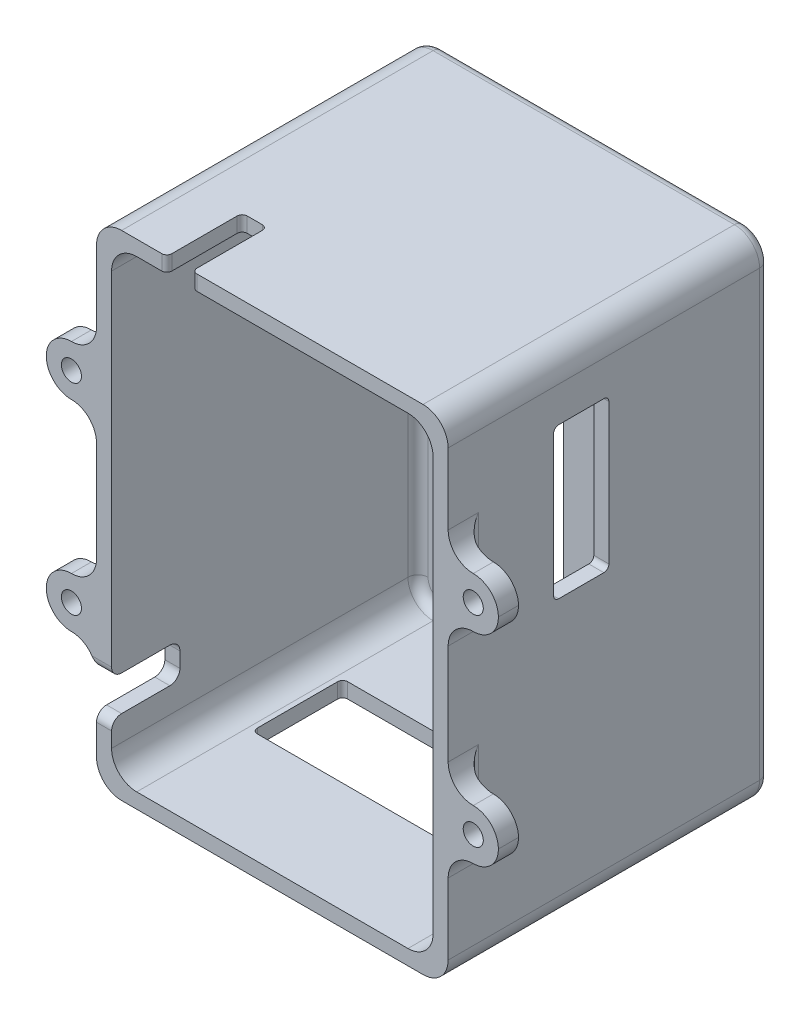
SolidWorks part; units mm, degrees
ref_plane "Front Plane" through (0, 0, 0) normal (0, 0, 1) x (1, 0, 0)
ref_plane "Top Plane" through (0, 0, 0) normal (0, 1, 0) x (1, 0, 0)
ref_plane "Right Plane" through (0, 0, 0) normal (1, 0, 0) x (0, 0, -1)
sketch "Sketch1" plane through (0, 0, 0) normal (0, 0, 1) x (1, 0, 0)
  line L1 (32, -46.1468) -> (-32, -46.1468)
  line L2 (32, -46.1468) -> (32, 46.1468)
  line L3 (32, 46.1468) -> (-32, 46.1468)
  line L4 (-32, -46.1468) -> (-32, 46.1468)
  line L5 (32, -46.1468) -> (-32, 46.1468) construction
  line L6 (32, 46.1468) -> (-32, -46.1468) construction
  line L12 (-19, -38.1468) -> (-29, -38.1468)
  line L13 (-19, -38.1468) -> (-19, 38.1468)
  line L14 (-19, 38.1468) -> (-29, 38.1468)
  line L15 (-29, -38.1468) -> (-29, 38.1468)
  line L16 (-19, -38.1468) -> (-29, 38.1468) construction
  line L17 (-19, 38.1468) -> (-29, -38.1468) construction
  line L69 (-3, -38.1468) -> (-3, 38.1468)
  line L70 (-3, -38.1468) -> (-13, -38.1468)
  line L71 (-13, -38.1468) -> (-13, 38.1468)
  line L72 (-3, 38.1468) -> (-13, 38.1468)
  line L73 (13, -38.1468) -> (13, 38.1468)
  line L74 (13, -38.1468) -> (3, -38.1468)
  line L75 (3, -38.1468) -> (3, 38.1468)
  line L76 (13, 38.1468) -> (3, 38.1468)
  line L100 (29, -38.1468) -> (29, 38.1468)
  line L101 (35, -49.1468) -> (-35, -49.1468)
  line L102 (35, -49.1468) -> (35, 49.1468)
  line L103 (35, 49.1468) -> (-35, 49.1468)
  line L104 (-35, -49.1468) -> (-35, 49.1468)
  line L105 (35, -49.1468) -> (-35, 49.1468) construction
  line L106 (35, 49.1468) -> (-35, -49.1468) construction
  line L107 (29, -38.1468) -> (19, -38.1468)
  line L108 (19, -38.1468) -> (19, 38.1468)
  line L109 (29, 38.1468) -> (19, 38.1468)
  point P0 (0, 0)
  point P7 (0, 0)
  point P8 (-24, 0)
  dimension "D1" = 64
  dimension "D2" = 8
  dimension "D3" = 8
  dimension "D4" = 3
  dimension "D5" = 10
  dimension "D6" = 3
  dimension "D8" = 3
  dimension "D9" = 3
  dimension "D10" = 92.2936
  dimension "D7" = 4
extrude "Boss-Extrude1" add sketch "Sketch1" along normal blind 3 contours L4 L1 L2 L3 L107 L12 L15 L14 L13 L74 region at (0, 0, 0)
extrude "Boss-Extrude2" add sketch "Sketch1<3>" along normal blind 64 contours L104 L101 L102 L103 L1 L4 L3 L2 region at (0, -47.9401, 0)
sketch "Sketch1<3>" plane through (0, 0, 0) normal (0, 0, 1) x (1, 0, 0) same geometry as "Sketch1"
fillet "Fillet1" radius 2 16 edges at (-29, 38.1468, 1.5) (-19, 38.1468, 1.5) (-29, -38.1468, 1.5) (-19, -38.1468, 1.5) (-13, -38.1468, 1.5) (-3, -38.1468, 1.5) (13, -38.1468, 1.5) (3, -38.1468, 1.5) (19, -38.1468, 1.5) (-3, 38.1468, 1.5) (13, 38.1468, 1.5) (-13, 38.1468, 1.5) (3, 38.1468, 1.5) (19, 38.1468, 1.5) (29, -38.1468, 1.5) (29, 38.1468, 1.5)
fillet "Fillet2" radius 5 8 edges at (-32, -46.1468, 33.5) (32, -46.1468, 33.5) (-32, 46.1468, 33.5) (32, 46.1468, 33.5) (35, -49.1468, 32) (-35, -49.1468, 32) (35, 49.1468, 32) (-35, 49.1468, 32)
sketch "Sketch2" plane through (0, 0, 0) normal (0, 1, 0) x (1, 0, 0)
  line L0 (30, -64) -> (-30, -64) construction
  line L1 (26, -42) -> (-26, -42)
  line L2 (26, -42) -> (26, -24)
  line L3 (26, -24) -> (-26, -24)
  line L4 (-26, -42) -> (-26, -24)
  line L5 (26, -42) -> (-26, -24) construction
  line L6 (26, -24) -> (-26, -42) construction
  line L8 (0, 0) -> (0, -66.913) construction
  point P0 (0, -33)
  dimension "D1" = 22
  dimension "D2" = 40
  dimension "D3" = 52
extrude "Cut-Extrude1" cut sketch "Sketch2" against normal blind 64
fillet "Fillet3" radius 1 4 edges at (-26, -47.6468, 42) (-26, -47.6468, 24) (26, -47.6468, 42) (26, -47.6468, 24)
sketch "Sketch3" plane through (0, 0, 0) normal (1, 0, 0) x (0, 0, -1)
  line L0 (-64, -44.1468) -> (-64, 44.1468) construction
  line L1 (-32, 7.1468) -> (-43, 7.1468)
  line L2 (-32, 7.1468) -> (-32, 37.1468)
  line L3 (-32, 37.1468) -> (-43, 37.1468)
  line L4 (-43, 7.1468) -> (-43, 37.1468)
  line L5 (-32, 7.1468) -> (-43, 37.1468) construction
  line L6 (-32, 37.1468) -> (-43, 7.1468) construction
  line L7 (-64, 49.1468) -> (0, 49.1468) construction
  point P0 (-37.5, 22.1468)
  dimension "D1" = 32
  dimension "D2" = 21
  dimension "D3" = 12
  dimension "D4" = 30
extrude "Cut-Extrude2" cut sketch "Sketch3" along normal blind 45
fillet "Fillet4" radius 1 4 edges at (33.5, 7.1468, 32) (33.5, 7.1468, 43) (33.5, 37.1468, 32) (33.5, 37.1468, 43)
sketch "Sketch4" plane through (0, 0, 0) normal (0, 1, 0) x (1, 0, 0)
  line L0 (-35, -64) -> (-35, 0) construction
  line L1 (-16, -64) -> (-21, -64)
  line L2 (-16, -64) -> (-16, -49)
  line L3 (-16, -49) -> (-21, -49)
  line L4 (-21, -64) -> (-21, -49)
  line L5 (-16, -64) -> (-21, -49) construction
  line L6 (-16, -49) -> (-21, -64) construction
  line L7 (30, -64) -> (-30, -64) construction
  point P0 (-18.5, -56.5)
  dimension "D1" = 15
  dimension "D2" = 14
  dimension "D3" = 5
extrude "Cut-Extrude3" cut sketch "Sketch4" along normal blind 81
fillet "Fillet5" radius 1 4 edges at (-21, 47.6468, 49) (-21, 47.6468, 64) (-16, 47.6468, 64) (-16, 47.6468, 49)
ref_plane "Plane1" through (0, 0, 64) normal (0, 0, 1) x (1, 0, 0)
sketch "Sketch5" plane through (0, 0, 64) normal (0, 0, 1) x (1, 0, 0)
  line L0 (35, -44.1468) -> (35, 44.1468) construction
  line L1 (35, 15) -> (45, 15)
  line L2 (35, 15) -> (35, 25)
  line L3 (35, 25) -> (45, 25)
  line L4 (45, 15) -> (45, 25)
  line L5 (35, 15) -> (45, 25) construction
  line L6 (35, 25) -> (45, 15) construction
  line L7 (0, 58.3443) -> (0, -58.3443) construction
  line L8 (48.8523, 0) -> (-42.1568, 0) construction
  line L9 (35, -25) -> (45, -15) construction
  line L10 (35, -15) -> (45, -25) construction
  line L11 (45, -15) -> (45, -25)
  line L12 (35, -25) -> (45, -25)
  line L13 (35, -15) -> (35, -25)
  line L14 (35, -15) -> (45, -15)
  line L15 (-35, -15) -> (-45, -25) construction
  line L16 (-35, -25) -> (-45, -15) construction
  line L17 (-35, 25) -> (-45, 15) construction
  line L18 (-35, 15) -> (-45, 25) construction
  line L19 (-35, -15) -> (-45, -15)
  line L20 (-35, -15) -> (-35, -25)
  line L21 (-35, -25) -> (-45, -25)
  line L22 (-45, -15) -> (-45, -25)
  line L23 (-45, 15) -> (-45, 25)
  line L24 (-35, 25) -> (-45, 25)
  line L25 (-35, 15) -> (-35, 25)
  line L26 (-35, 15) -> (-45, 15)
  circle A0 centre (40, 20) radius 2
  circle A1 centre (40, -20) radius 2
  circle A2 centre (-40, 20) radius 2
  circle A3 centre (-40, -20) radius 2
  point P0 (40, 20)
  point P16 (40, -20)
  point P25 (-40, -20)
  point P26 (-40, 20)
  dimension "D4" = 4
  dimension "D5" = 4
  dimension "D6" = 4
  dimension "D7" = 4
  dimension "D1" = 10
  dimension "D2" = 10
  dimension "D3" = 20
extrude "Boss-Extrude3" add sketch "Sketch5" against normal blind 4
fillet "Fillet6" radius 5 8 edges at (35, 25, 62) (35, 15, 62) (35, -15, 62) (35, -25, 62) (-35, 25, 62) (-35, 15, 62) (-35, -15, 62) (-35, -25, 62)
fillet "Fillet7" radius 5 8 edges at (-45, 25, 62) (-45, 15, 62) (-45, -15, 62) (-45, -25, 62) (45, -25, 62) (45, -15, 62) (45, 15, 62) (45, 25, 62)
fillet "Fillet8" radius 2 4 edges at (35, -20, 60) (35, 20, 60) (-35, 20, 60) (-35, -20, 60)
fillet "Fillet9" radius 2 8 edges at (-33.5355, -47.6823, 0) (0, -49.1468, 0) (33.5355, -47.6823, 0) (35, 0, 0) (33.5355, 47.6823, 0) (-33.5355, 47.6823, 0) (0, 49.1468, 0) (-35, 0, 0)
fillet "Fillet10" radius 2 8 edges at (30.5355, -44.6823, 3) (0, -46.1468, 3) (-30.5355, -44.6823, 3) (-32, 0, 3) (-30.5355, 44.6823, 3) (32, 0, 3) (30.5355, 44.6823, 3) (0, 46.1468, 3)
sketch "Sketch6" plane through (0, 0, 0) normal (1, 0, 0) x (0, 0, -1)
  line L0 (-64, -44.1468) -> (-64, -30) construction
  line L1 (-64, -36.1468) -> (-50.4, -36.1468)
  line L2 (-64, -36.1468) -> (-64, -29.1468)
  line L3 (-64, -29.1468) -> (-50.4, -29.1468)
  line L4 (-50.4, -36.1468) -> (-50.4, -29.1468)
  line L5 (-64, -36.1468) -> (-50.4, -29.1468) construction
  line L6 (-64, -29.1468) -> (-50.4, -36.1468) construction
  line L7 (-25, -46.1468) -> (-41, -46.1468) construction
  point P0 (-57.2, -32.6468)
  dimension "D1" = 7
  dimension "D2" = 10
  dimension "D3" = 13.6
extrude "Cut-Extrude4" cut sketch "Sketch6" against normal blind 48
fillet "Fillet11" radius 2 4 edges at (-33.5, -36.1468, 64) (-33.5367, -29.1468, 64) (-33.5, -36.1468, 50.4) (-33.5, -29.1468, 50.4)
